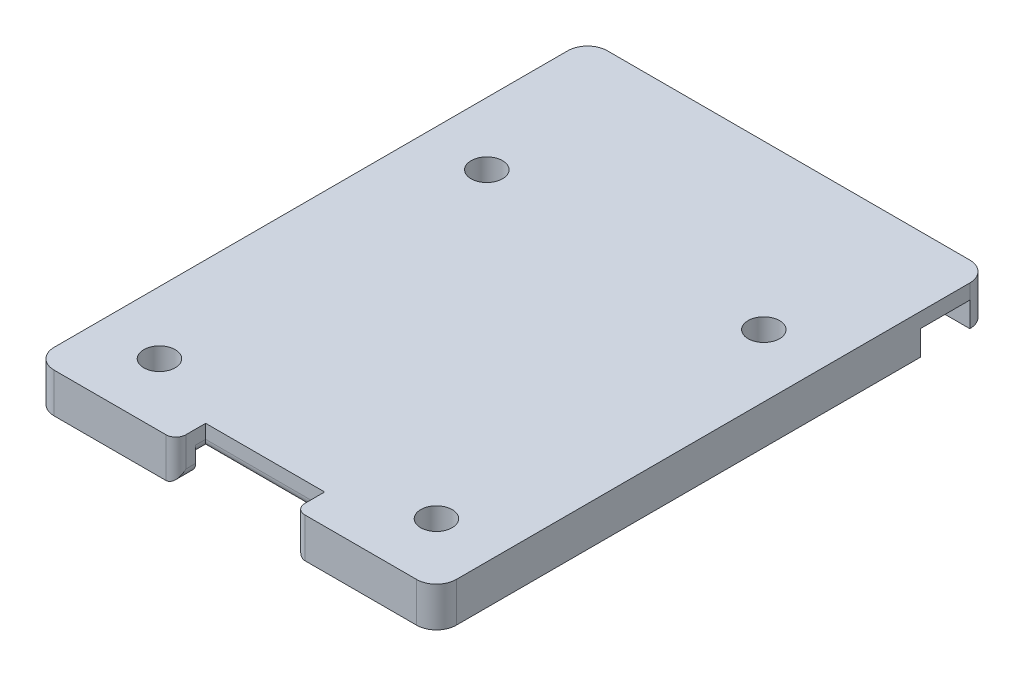
SolidWorks part; units mm, degrees
ref_plane "Front Plane" through (0, 0, 0) normal (0, 0, 1) x (1, 0, 0)
ref_plane "Top Plane" through (0, 0, 0) normal (0, 1, 0) x (1, 0, 0)
ref_plane "Right Plane" through (0, 0, 0) normal (1, 0, 0) x (0, 0, -1)
sketch "Sketch1" plane through (0, 0, 0) normal (0, 1, 0) x (1, 0, 0)
  line L1 (-7.3177, 20.9633) -> (28.2423, 20.9633)
  line L2 (-7.3177, 20.9633) -> (-7.3177, -29.8367)
  line L3 (-7.3177, -29.8367) -> (28.2423, -29.8367)
  line L4 (28.2423, 20.9633) -> (28.2423, -29.8367)
  line L5 (-7.8177, 21.4633) -> (28.7423, 21.4633)
  line L6 (-7.8177, 21.4633) -> (-7.8177, -30.3367)
  line L7 (-7.8177, -30.3367) -> (28.7423, -30.3367)
  line L8 (28.7423, 21.4633) -> (28.7423, -30.3367)
  line L9 (-9.8177, 23.4633) -> (30.7423, 23.4633)
  line L10 (-9.8177, 23.4633) -> (-9.8177, -32.3367)
  line L11 (-9.8177, -32.3367) -> (30.7423, -32.3367)
  line L12 (30.7423, 23.4633) -> (30.7423, -32.3367)
  circle A0 centre (-3.5077, 6.9933) radius 1.5875
  circle A1 centre (24.4323, 6.9933) radius 1.5875
  circle A2 centre (-3.5077, -26.0267) radius 1.5875
  circle A3 centre (24.4323, -26.0267) radius 1.5875
  dimension "D3" = 3.175
  dimension "D4" = 3.175
  dimension "D5" = 3.175
  dimension "D6" = 3.175
  dimension "D1" = 50.8
  dimension "D2" = 35.56
  dimension "D7" = 3.81
  dimension "D8" = 3.81
  dimension "D9" = 3.81
  dimension "D10" = 3.81
  dimension "D11" = 27.94
  dimension "D12" = 33.02
  dimension "D13" = 27.94
  dimension "D14" = 3.81
  dimension "D15" = 0.5
  dimension "D16" = 0.5
  dimension "D17" = 0.5
  dimension "D18" = 0.5
  dimension "D19" = 2
  dimension "D20" = 2
  dimension "D21" = 2
  dimension "D22" = 2
extrude "Boss-Extrude2" add sketch "Sketch1" along normal blind 4 contours A1 | L9 L12 L11 L10 | A0 | A2 | A3 region at (24.4323, 0, -6.9933)
extrude "Cut-Extrude1" cut sketch "Sketch1<4>" along normal blind 1.6 contours L5 L8 L7 L6
sketch "Sketch1<4>" plane through (0, 0, 0) normal (0, 1, 0) x (1, 0, 0) same geometry as "Sketch1"
sketch "Sketch3" plane through (0, 1.6, 0) normal (0, -1, 0) x (1, 0, 0)
  line L0 (-7.8177, -21.4633) -> (-7.8177, 30.3367) construction
  line L1 (-7.3177, -15.4633) -> (28.2423, -15.4633)
  line L2 (-7.3177, -15.4633) -> (-7.3177, -19.4633)
  line L3 (-7.3177, -19.4633) -> (28.2423, -19.4633)
  line L4 (28.2423, -15.4633) -> (28.2423, -19.4633)
  line L5 (28.7423, -21.4633) -> (28.7423, 30.3367) construction
  line L6 (-7.8177, -21.4633) -> (28.7423, -21.4633) construction
  line L7 (-7.8177, -21.4633) -> (-7.8177, 30.3367) construction
  line L8 (2.1823, 28.3367) -> (18.7423, 28.3367)
  line L9 (2.1823, 28.3367) -> (2.1823, 18.3367)
  line L10 (2.1823, 18.3367) -> (18.7423, 18.3367)
  line L11 (18.7423, 28.3367) -> (18.7423, 18.3367)
  line L12 (-7.8177, 30.3367) -> (28.7423, 30.3367) construction
  line L13 (-7.8177, 30.3367) -> (28.7423, 30.3367) construction
  line L14 (4.1823, 16.3367) -> (27.2423, 16.3367)
  line L15 (4.1823, 16.3367) -> (4.1823, 2.3367)
  line L16 (4.1823, 2.3367) -> (27.2423, 2.3367)
  line L17 (27.2423, 16.3367) -> (27.2423, 2.3367)
  dimension "D1" = 0.5
  dimension "D2" = 0.5
  dimension "D3" = 2
  dimension "D4" = 4
  dimension "D5" = 10
  dimension "D6" = 10
  dimension "D7" = 2
  dimension "D8" = 10
  dimension "D9" = 28
  dimension "D10" = 1.5
  dimension "D11" = 14
  dimension "D12" = 12
extrude "Cut-Extrude2" cut sketch "Sketch3" against normal blind 1.6002
sketch "Sketch4" plane through (0, 0, 0) normal (0, -1, 0) x (1, 0, 0)
  line L0 (30.7423, -23.4633) -> (30.7423, 32.3367) construction
  line L1 (28.7423, -21.4633) -> (30.7423, -21.4633)
  line L2 (28.7423, -21.4633) -> (28.7423, -16.4633)
  line L3 (28.7423, -16.4633) -> (30.7423, -16.4633)
  line L4 (30.7423, -21.4633) -> (30.7423, -16.4633)
  line L5 (-9.8177, -23.4633) -> (-9.8177, 32.3367) construction
  line L6 (-7.8177, -21.4633) -> (-9.8177, -21.4633)
  line L7 (-7.8177, -21.4633) -> (-7.8177, -16.4633)
  line L8 (-7.8177, -16.4633) -> (-9.8177, -16.4633)
  line L9 (-9.8177, -21.4633) -> (-9.8177, -16.4633)
  line L10 (-9.8177, -23.4633) -> (30.7423, -23.4633) construction
  dimension "D1" = 5
  dimension "D2" = 5
  dimension "D3" = 2
  dimension "D4" = 2
extrude "Cut-Extrude3" cut sketch "Sketch4" against normal blind 2.5
sketch "Sketch5" plane through (0, 0, 32.3367) normal (0, 0, -1) x (-1, 0, 0)
  line L0 (9.8177, 4) -> (-30.7423, 4) construction
  line L1 (-16.4623, 4) -> (-4.4623, 4)
  line L2 (-16.4623, 4) -> (-16.4623, -5.591)
  line L3 (-16.4623, -5.591) -> (-4.4623, -5.591)
  line L4 (-4.4623, 4) -> (-4.4623, -5.591)
  point P6 (-10.4623, 4)
  dimension "D1" = 12
extrude "Cut-Extrude4" cut sketch "Sketch5" along normal blind 3
fillet "Fillet1" radius 2 4 edges at (30.7423, 2, -23.4633) (-9.8177, 2, -23.4633) (-9.8177, 2, 32.3367) (30.7423, 2, 32.3367)
fillet "Fillet2" radius 1 7 edges at (4.4623, 0, 31.3367) (16.4623, 0, 31.3367) (16.4623, 1.6, 29.8367) (4.4623, 1.6, 29.8367) (10.4623, 1.6, 29.3367) (16.4623, 2, 32.3367) (4.4623, 2, 32.3367)
